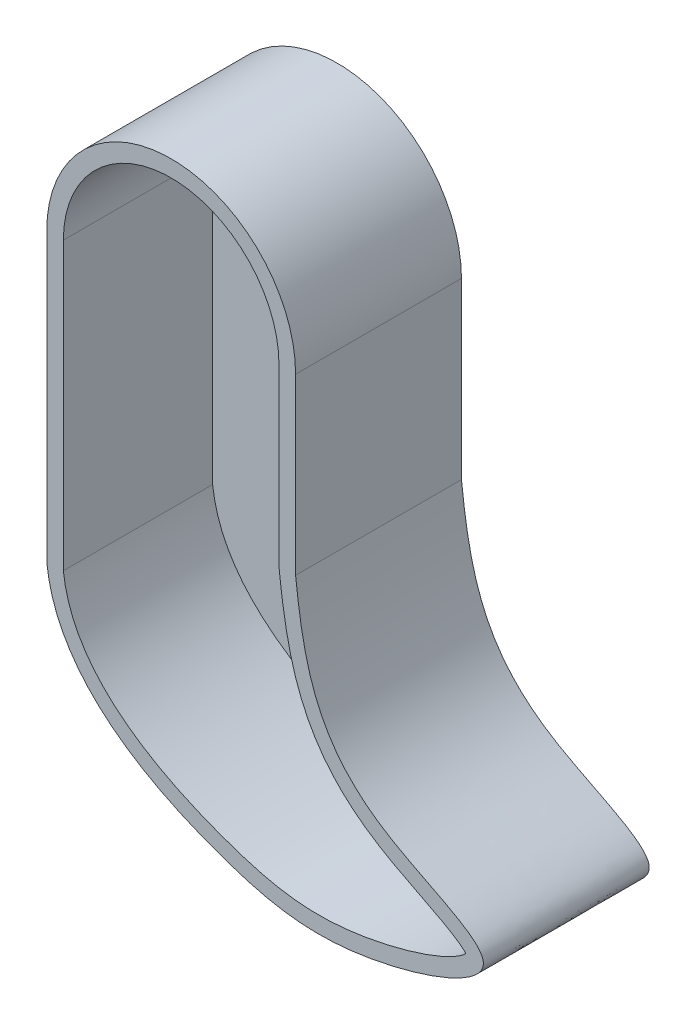
SolidWorks part; units mm, degrees
ref_plane "前视基准面" through (0, 0, 0) normal (0, 0, 1) x (1, 0, 0)
ref_plane "上视基准面" through (0, 0, 0) normal (0, 1, 0) x (1, 0, 0)
ref_plane "右视基准面" through (0, 0, 0) normal (1, 0, 0) x (0, 0, -1)
sketch "草图1" plane through (0, 0, 0) normal (0, 0, 1) x (1, 0, 0)
  line L0 (7.5, 0) -> (7.5, -10.5047)
  line L1 (-7.5, 0) -> (-7.5, -17.3169)
  arc A0 (7.5, 0) -> (-7.5, 0) centre (0, 0) ccw
  spline S0 degree 3 poles (7.5, -10.5047) (8.0213, -15.2017) (9.3059, -20.5609) (22.6748, -25.2262) (10.3405, -29.3227) (1.3636, -27.3729) (-6.8963, -22.8796) (-7.5, -17.3169) knots 0 0 0 0 0.243808 0.379428 0.541668 0.697633 1 1 1 1
  dimension "D1" = 15
extrude "凸台-拉伸1" add sketch "草图1" along normal blind 10
shell "抽壳1" thickness 1 removed face at (-1.875, -5.9319, 10)
sketch "草图2" plane through (0, 0, 0) normal (0, 0, -1) x (-1, 0, 0)
  circle A0 centre (0, 0) radius 2.5
  dimension "D1" = 5
extrude "切除-拉伸1" cut sketch "草图2" against normal blind 10
